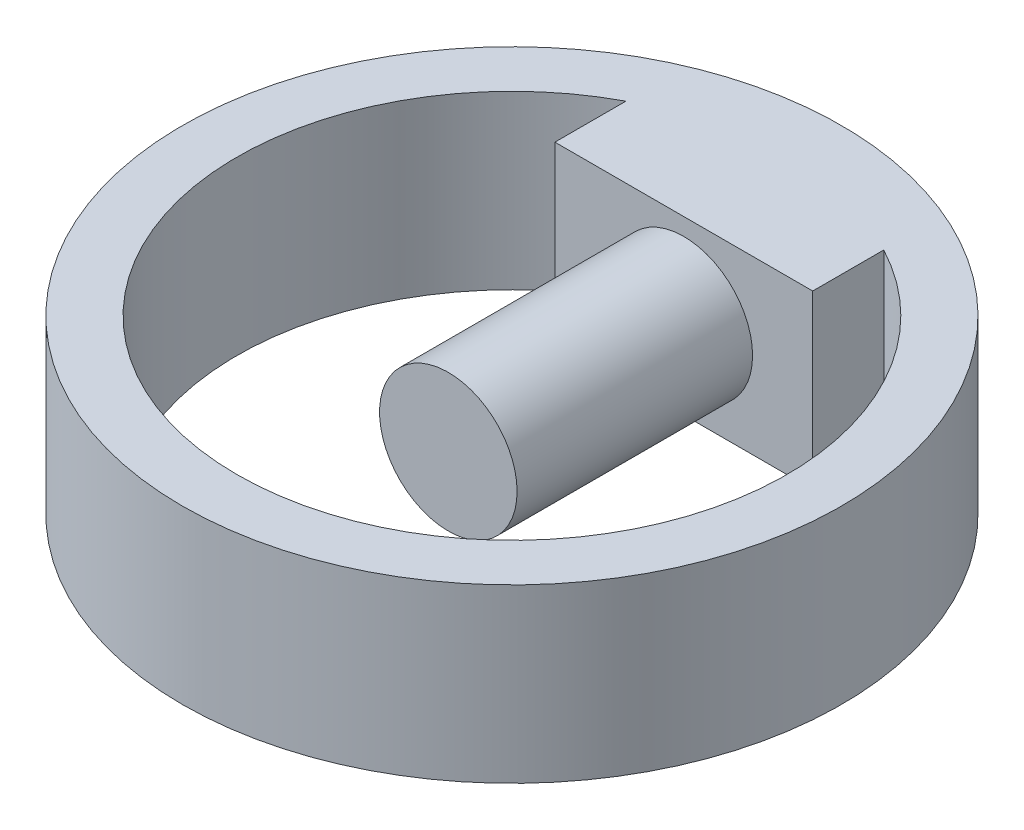
SolidWorks part; units mm, degrees
ref_plane "Top Plane" through (0, 0, 0) normal (0, 0, 1) x (1, 0, 0)
ref_plane "Right Plane" through (0, 0, 0) normal (0, 1, 0) x (1, 0, 0)
ref_plane "Front Plane" through (0, 0, 0) normal (1, 0, 0) x (0, 0, -1)
ref_axis "x-axis" through (-88.99, 0, 0) along (1, 0, 0)
ref_axis "y-axis" through (0, -55, 0) along (0, 1, 0)
ref_axis "z-axis" through (0, 0, 55) along (0, 0, -1)
sketch "Sketch6" plane through (0, 0, 0) normal (0, 1, 0) x (1, 0, 0)
  circle A0 centre (0, 0) radius 16
  circle A1 centre (0, 0) radius 19.175
  dimension "D1" = 3.175
  dimension "D2" = 32
extrude "Boss-Extrude4" add sketch "Sketch6" along normal mid plane 10
ref_plane "Plane3" through (0, 0, 3.7) normal (0, 0, 1) x (1, 0, 0)
sketch "Sketch7" plane through (0, 0, 3.7) normal (0, 0, 1) x (1, 0, 0)
  circle A0 centre (0, 0) radius 4
  dimension "D1" = 8
extrude "Boss-Extrude5" add sketch "Sketch7" against normal up to next
ref_plane "Plane2" through (0, 0, -10) normal (0, 0, 1) x (1, 0, 0)
sketch "Sketch8" plane through (0, 0, -10) normal (0, 0, 1) x (1, 0, 0)
  line L0 (16, 5) -> (-16, 5) construction
  line L1 (-7.5, 5) -> (7.5, 5)
  line L2 (-7.5, 5) -> (-7.5, -5)
  line L3 (-7.5, -5) -> (7.5, -5)
  line L4 (7.5, 5) -> (7.5, -5)
  line L5 (-7.5, 5) -> (7.5, -5) construction
  line L6 (-7.5, -5) -> (7.5, 5) construction
  point P0 (0, 0)
  point P5 (6.2267, 5)
  dimension "D1" = 15
extrude "Boss-Extrude6" add sketch "Sketch8" against normal up to next
